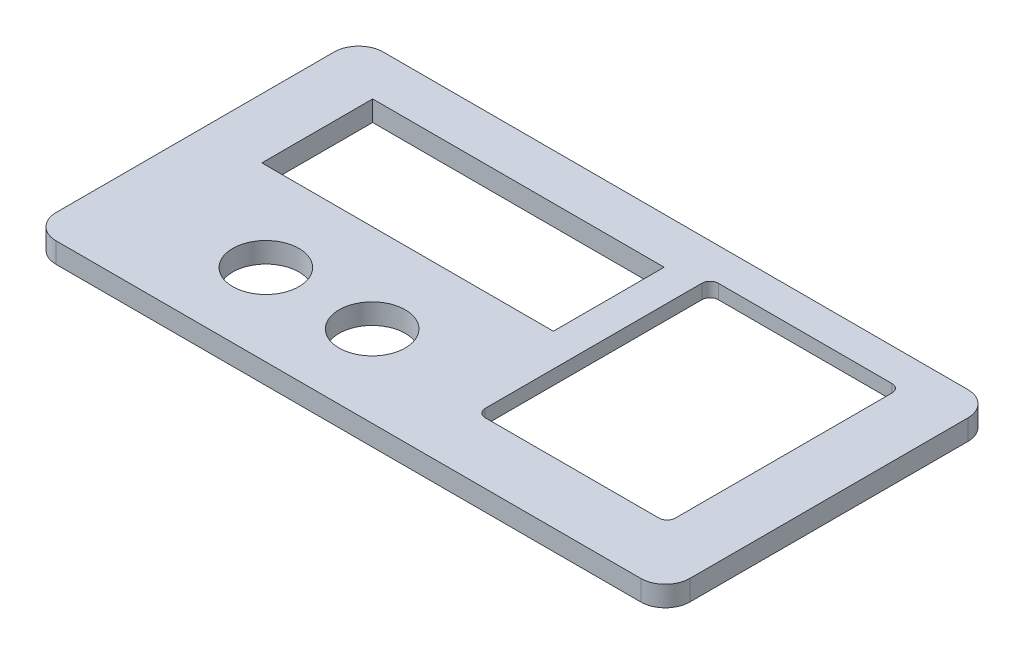
SolidWorks part; units mm, degrees
ref_plane "Front Plane" through (0, 0, 0) normal (0, 0, 1) x (1, 0, 0)
ref_plane "Top Plane" through (0, 0, 0) normal (0, 1, 0) x (1, 0, 0)
ref_plane "Right Plane" through (0, 0, 0) normal (1, 0, 0) x (0, 0, -1)
sketch "Sketch1" plane through (0, 0, 0) normal (0, 1, 0) x (1, 0, 0)
  line L1 (-77.5, -40) -> (77.5, -40)
  line L2 (-77.5, -40) -> (-77.5, 40)
  line L3 (-77.5, 40) -> (77.5, 40)
  line L4 (77.5, -40) -> (77.5, 40)
  line L5 (-77.5, -40) -> (77.5, 40) construction
  line L6 (-77.5, 40) -> (77.5, -40) construction
  point P0 (0, 0)
  dimension "D1" = 155
  dimension "D2" = 80
extrude "Boss-Extrude1" add sketch "Sketch1" along normal blind 5
sketch "Sketch2" plane through (0, 0, 0) normal (0, 1, 0) x (1, 0, 0)
  line L1 (-62.8518, 1.6691) -> (8.446, 1.6691)
  line L2 (-62.8518, 1.6691) -> (-62.8518, 28.7709)
  line L3 (-62.8518, 28.7709) -> (8.446, 28.7709)
  line L4 (8.446, 1.6691) -> (8.446, 28.7709)
  line L5 (-62.8518, 1.6691) -> (8.446, 28.7709) construction
  line L6 (-62.8518, 28.7709) -> (8.446, 1.6691) construction
  line L7 (-67.5, 15.22) -> (12.51, 15.22) construction
  line L8 (-67.5, 33) -> (12.51, 33) construction
  line L9 (-67.5, 33) -> (-67.5, -2.56) construction
  line L10 (-67.5, -2.56) -> (12.51, -2.56) construction
  line L11 (12.51, 33) -> (12.51, -2.56) construction
  line L12 (77.5, 40) -> (-77.5, 40) construction
  line L13 (-77.5, 40) -> (-77.5, -40) construction
  circle A0 centre (-64.96, -0.02) radius 1.5
  circle A1 centre (9.97, -0.02) radius 1.5
  circle A2 centre (9.97, 30.46) radius 1.5
  circle A3 centre (-64.96, 30.46) radius 1.5
  point P0 (-27.2029, 15.22)
  point P6 (-27.2029, 17.22)
  point P20 (-27.495, 15.22)
  dimension "D7" = 2.54
  dimension "D8" = 3
  dimension "D1" = 71.2978
  dimension "D2" = 27.1018
  dimension "D3" = 7
  dimension "D4" = 35.56
  dimension "D5" = 80.01
  dimension "D6" = 4.6482
  dimension "D9" = 33.02
  dimension "D10" = 77.47
  dimension "D11" = 5.08
  dimension "D12" = 10
extrude "Screen Cutout" cut sketch "Sketch2" along normal through all contours L2 L1 L4 L3
extrude "Cut-Extrude4" cut sketch "Sketch2<3>" along normal blind 2.9
sketch "Sketch2<3>" plane through (0, 0, 0) normal (0, 1, 0) x (1, 0, 0) same geometry as "Sketch2"
sketch "Sketch3" plane through (0, 0, 0) normal (0, 1, 0) x (1, 0, 0)
  line L0 (-40.2029, -20) -> (-14.2029, -20) construction
  line L1 (-48.3529, -11.45) -> (-48.3529, -28.55) construction
  line L2 (-48.3529, -28.55) -> (-6.0529, -28.55) construction
  line L3 (-62.8518, 1.6691) -> (8.446, 1.6691) construction
  line L4 (-77.5, -40) -> (77.5, -40) construction
  line L7 (-27.2029, 26.9252) -> (-27.2029, -22.8987) construction
  circle A0 centre (-40.2029, -20) radius 8.1
  circle A1 centre (-14.2029, -20) radius 8.1
  circle A2 centre (-48.3529, -11.45) radius 1.1906
  circle A3 centre (-6.0529, -11.45) radius 1.1906
  circle A4 centre (-6.0529, -28.55) radius 1.1906
  circle A5 centre (-48.3529, -28.55) radius 1.1906
  point P4 (-27.2029, -28.55)
  point P14 (-27.2029, -20)
  point P19 (-27.2029, 1.6691)
  dimension "D1" = 16.2
  dimension "D2" = 26
  dimension "D3" = 2.3813
  dimension "D4" = 17.1
  dimension "D5" = 20
  dimension "D6" = 42.3
  dimension "D7" = 8.55
extrude "Ultrasound Cutouts" cut sketch "Sketch3" along normal through all contours A1 | A0
extrude "Cut-Extrude2" cut sketch "Sketch3<3>" along normal blind 3.175
sketch "Sketch3<3>" plane through (0, 0, 0) normal (0, 1, 0) x (1, 0, 0) same geometry as "Sketch3"
sketch "Sketch4" plane through (0, 5, 0) normal (0, 1, 0) x (1, 0, 0)
  circle A0 centre (-21.6513, -28.8183) radius 0.85
  circle A1 centre (20.3487, -11.8183) radius 0.85
  circle A2 centre (-21.6513, -11.8183) radius 0.85
  circle A3 centre (20.3487, -28.8183) radius 0.85
  dimension "D1" = 1.7
  dimension "D2" = 17
  dimension "D3" = 42
extrude "Ultrasound Bolt Holes" [suppressed] cut sketch "Sketch4" against normal through all
sketch "Sketch5" plane through (0, 0, 0) normal (0, -1, 0) x (1, 0, 0)
  line L0 (-6.322, 30.05) -> (-48.622, 30.05) construction
  line L1 (-21.472, 30.05) -> (-33.472, 30.05)
  line L2 (-21.472, 30.05) -> (-21.472, 25.05)
  line L3 (-21.472, 25.05) -> (-33.472, 25.05)
  line L4 (-33.472, 30.05) -> (-33.472, 25.05)
  line L5 (-21.472, 30.05) -> (-33.472, 25.05) construction
  line L6 (-21.472, 25.05) -> (-33.472, 30.05) construction
  circle A1 centre (-6.0529, 28.55) radius 1.1906 construction
  point P0 (-27.472, 27.55)
  point P13 (-27.472, 30.05)
  point P14 (-27.472, 30.05)
  dimension "D3" = 1.5
  dimension "D1" = 12
  dimension "D2" = 5
extrude "US Clock cutout" cut sketch "Sketch5" against normal blind 4
sketch "Sketch6" plane through (0, 0, 0) normal (0, -1, 0) x (1, 0, 0)
  line L0 (-21.472, 27.55) -> (-33.472, 27.55) construction
  line L1 (-22.472, 13.3) -> (-32.472, 13.3)
  line L2 (-22.472, 13.3) -> (-22.472, 9.8)
  line L3 (-22.472, 9.8) -> (-32.472, 9.8)
  line L4 (-32.472, 13.3) -> (-32.472, 9.8)
  line L5 (-22.472, 13.3) -> (-32.472, 9.8) construction
  line L6 (-22.472, 9.8) -> (-32.472, 13.3) construction
  line L7 (-21.472, 25.05) -> (-21.472, 30.05) construction
  line L8 (-33.472, 30.05) -> (-33.472, 25.05) construction
  line L9 (-6.6073, 10.2724) -> (-48.9073, 10.2724) construction
  line L10 (-27.472, 5.8213) -> (-27.472, 1.0358) construction
  point P0 (-27.472, 11.55)
  point P19 (0, 0)
  point P20 (-27.472, 27.55)
  dimension "D1" = 10
  dimension "D2" = 3.5
  dimension "D3" = 16
extrude "US Pin cutout" cut sketch "Sketch6" against normal blind 2
fillet "Fillet2" [suppressed] radius 1
ref_plane "Magnet plane" through (0, 0.2, 0) normal (0, -1, 0) x (-1, 0, 0)
sketch "Sketch9" plane through (0, 0.2, 0) normal (0, -1, 0) x (-1, 0, 0)
  line L0 (-77.5, -40) -> (-77.5, 40) construction
  line L1 (-77.5, 40) -> (77.5, 40) construction
  line L2 (77.5, -40) -> (-77.5, -40) construction
  line L3 (77.5, 40) -> (77.5, -40) construction
  circle A0 centre (-71.5, 34) radius 3.15
  circle A1 centre (71.5, 34) radius 3.15
  circle A2 centre (-71.5, -34) radius 3.15
  circle A3 centre (71.5, -34) radius 3.15
  dimension "D1" = 6.3
  dimension "D2" = 6
  dimension "D3" = 6
  dimension "D4" = 6
  dimension "D5" = 6
extrude "Magnet Holes" cut sketch "Sketch9" against normal blind 2.1
fillet "Fillet1" radius 6 4 edges at (77.5, 2.5, -40) (77.5, 2.5, 40) (-77.5, 2.5, 40) (-77.5, 2.5, -40)
sketch "Sketch10" plane through (0, 5, 0) normal (0, 1, 0) x (1, 0, 0)
  line L0 (8.446, 1.6691) -> (8.446, 28.7709) construction
  line L1 (16.446, -25) -> (62.946, -25)
  line L2 (16.446, -25) -> (16.446, 32)
  line L3 (16.446, 32) -> (62.946, 32)
  line L4 (62.946, -25) -> (62.946, 32)
  line L5 (16.446, -25) -> (62.946, 32) construction
  line L6 (16.446, 32) -> (62.946, -25) construction
  line L7 (71.5, 40) -> (-71.5, 40) construction
  point P0 (39.696, 3.5)
  dimension "D1" = 46.5
  dimension "D2" = 57
  dimension "D3" = 8
  dimension "D4" = 8
extrude "Keypad cutout" cut sketch "Sketch10" against normal through all
sketch "Sketch11" plane through (0, 0, 0) normal (0, -1, 0) x (1, 0, 0)
  line L0 (58.696, 34.5) -> (58.696, 28.5)
  line L1 (65.696, -35.5) -> (13.696, -35.5)
  line L2 (65.696, -35.5) -> (65.696, 28.5)
  line L3 (65.696, 28.5) -> (13.696, 28.5)
  line L4 (13.696, -35.5) -> (13.696, 28.5)
  line L5 (58.696, 34.5) -> (20.696, 34.5)
  line L6 (58.696, 28.5) -> (20.696, 28.5)
  line L7 (20.696, 34.5) -> (20.696, 28.5)
  line L8 (58.696, 34.5) -> (20.696, 28.5) construction
  line L9 (58.696, 28.5) -> (20.696, 34.5) construction
  line L10 (62.946, -32) -> (16.446, 25) construction
  line L11 (16.446, -32) -> (62.946, 25) construction
  line L12 (39.696, 25.3529) -> (39.696, -31.6471) construction
  line L14 (62.946, -3.5) -> (16.446, -3.5) construction
  point P4 (39.696, 28.5)
  point P5 (39.696, 31.5)
  point P6 (39.696, 28.5)
  point P16 (39.696, -35.5)
  point P23 (65.696, -3.5)
  point P24 (39.696, -3.5)
  line M12 (62.946, 25) -> (62.946, -32)
  line M13 (62.946, -32) -> (16.446, -32)
  line M14 (16.446, -32) -> (16.446, 25)
  line M15 (16.446, 25) -> (62.946, 25)
  dimension "D1" = 52
  dimension "D2" = 64
  dimension "D3" = 38
  dimension "D4" = 6
extrude "Cut-Extrude1" cut sketch "Sketch11" against normal blind 1.5 contours M12 M15 M14 M13 | L4 L1 L2 L3 M15 M12 M13 M14 | L5 L7 L3 L0 region at (39.696, 0, 31.5) region at (62.196, 0, 27.6754) region at (39.696, 0, -3.5)
fillet "Fillet3" radius 2 4 edges at (65.696, 0.75, 28.5) (13.696, 0.75, 28.5) (13.696, 0.75, -35.5) (65.696, 0.75, -35.5)
fillet "Fillet4" radius 2 4 edges at (62.946, 3.25, 25) (16.446, 3.25, 25) (16.446, 3.25, -32) (62.946, 3.25, -32)
sketch "Sketch12" plane through (0, 1.5, 0) normal (0, -1, 0) x (1, 0, 0)
  circle A0 centre (63.092, -34.1237) radius 1.5
  circle A1 centre (15.8391, -34.1237) radius 1.5
  circle A2 centre (15.8391, 26.403) radius 1.5
  circle A3 centre (63.092, 26.403) radius 1.5
  point P8 (0, 0)
  point P9 (0, 0)
  point P10 (0, 0)
  point P11 (0, 0)
  point P12 (17.0318, 23)
  point P13 (15.8391, 26.403)
  dimension "D1" = 3
extrude "Cut-Extrude3" cut sketch "Sketch12" against normal blind 2.9
